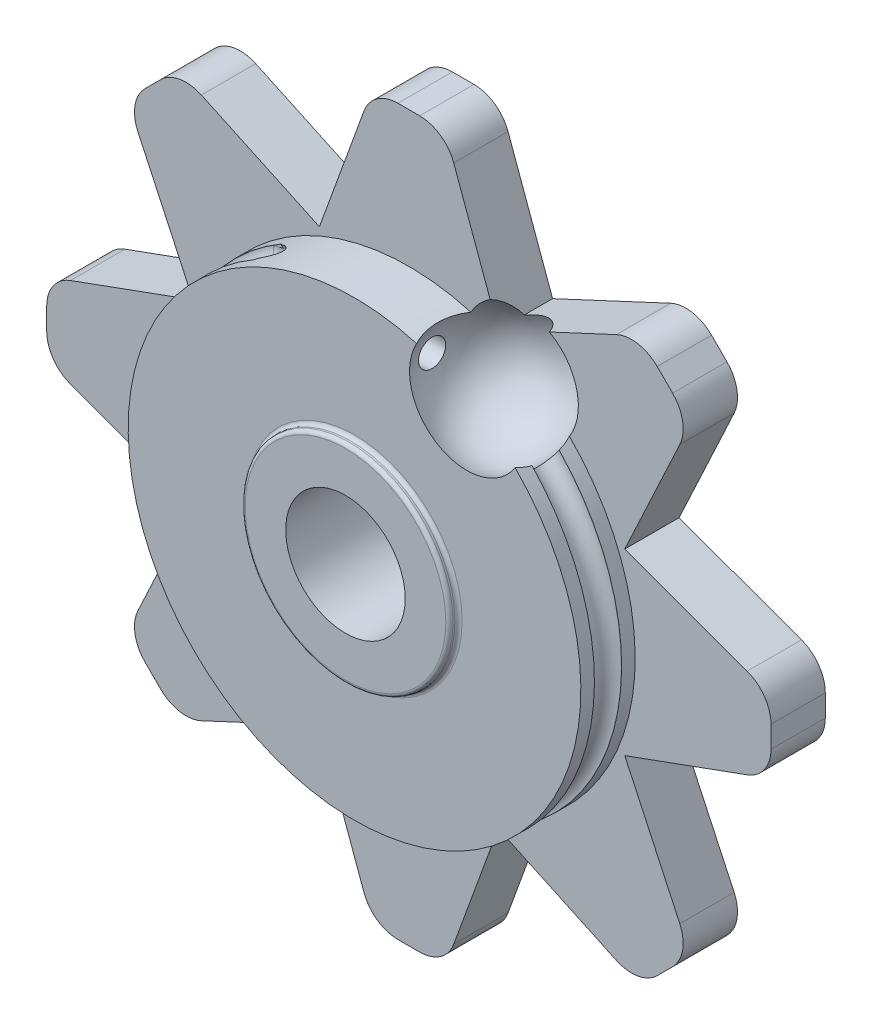
SolidWorks part; units mm, degrees
ref_plane "Front Plane" through (0, 0, 0) normal (0, 0, 1) x (1, 0, 0)
ref_plane "Top Plane" through (0, 0, 0) normal (0, 1, 0) x (1, 0, 0)
ref_plane "Right Plane" through (0, 0, 0) normal (1, 0, 0) x (0, 0, -1)
ref_axis "Axis1" through (-15.7375, 0, 0) along (1, 0, 0)
ref_axis "Axis2" through (0, 0, 2.1063) along (0, 0, -1)
ref_plane "Plane5" through (0, 0, 0) normal (0.866, 0.5, 0) x (0, 0, -1)
ref_plane "Plane6" through (3.1, 0, 0) normal (1, 0, 0) x (0, 0, -1)
sketch "Sketch1" plane through (0, 0, 0) normal (0, 0, 1) x (1, 0, 0)
  line L0 (-15.7375, 0) -> (15.7375, 0) construction
  circle A0 centre (0, 0) radius 6.25
  dimension "D1" = 12.5
extrude "body" add sketch "Sketch1" along normal blind 1.5 contours A0
sketch "Sketch2" plane through (0, 0, 0) normal (1, 0, 0) x (0, 0, -1)
  line L1 (0, 6.25) -> (-1.5, 6.25) construction
  line L2 (0, 5.25) -> (-1.5, 5.25) construction
  line L3 (-0.75, 5.25) -> (-0.75, -4.75) construction
  line L4 (0, -6.25) -> (0, 6.25) construction
  line L5 (0, -6.25) -> (0, 6.25) construction
  circle A0 centre (-0.75, 5.25) radius 0.375
  circle A1 centre (-0.75, -4.75) radius 0.375
  dimension "D1" = 0.75
  dimension "D3" = 0.75
  dimension "D4" = 1.5
  dimension "D2" = 1
extrude "Hole to trap cable knot" cut sketch "Sketch2" against normal through all and the other way blind 10 contours A0 | A1
ref_plane "Plane1" through (0, 0, 1.875) normal (0, 0, 1) x (1, 0, 0)
sketch "Sketch6" plane through (0, 0, 1.875) normal (0, 0, 1) x (1, 0, 0)
  line L0 (1.3991, -2.4232) -> (-1.3991, 2.4232) construction
  arc A0 (3.9111, 4.875) -> (2.7243, 5.625) centre (0, 0) ccw construction
  circle A2 centre (0, 0) radius 6.25 construction
  arc A3 (-3.125, 5.4127) -> (3.2608, 5.332) centre (0, 0) ccw
  arc A4 (3.9111, 4.875) -> (2.7243, 5.625) centre (0, 0) ccw construction
sketch "Sketch10" plane through (-5.4127, 9.375, 0) normal (-0.866, -0.5, 0) x (-0.5, 0.866, 0)
  line L0 (-4.5831, -1.125) -> (-3.8727, -1.125)
  line L1 (-3.8727, -1.125) -> (-3.8727, -0.3748)
  line L2 (-3.8727, -0.3748) -> (-4.5831, -0.3748)
  arc A0 (-4.5831, -0.3748) -> (-4.5831, -1.125) centre (-4.5831, -0.7499) ccw
  spline S0 degree 3 poles (-4.5903, -1.125) (-4.5759, -1.125) (-4.5739, -1.1025) (-4.5775, -1.0318) (-4.5799, -1.0018) (-4.5843, -0.9422) (-4.5859, -0.9199) (-4.589, -0.8665) (-4.5904, -0.8353) (-4.592, -0.7664) (-4.5919, -0.7281) (-4.5902, -0.6593) (-4.5887, -0.6289) (-4.5841, -0.5506) (-4.5809, -0.5129) (-4.5744, -0.422) (-4.574, -0.3902) (-4.5837, -0.3678) (-4.5938, -0.3778) (-4.6147, -0.4453) (-4.6227, -0.4771) (-4.6376, -0.5669) (-4.6447, -0.6281) (-4.6494, -0.7694) (-4.6461, -0.8461) (-4.6338, -0.9631) (-4.6257, -1.0065) (-4.603, -1.1026) (-4.5903, -1.125) (-4.5759, -1.125) (-4.5739, -1.1025) knots -0.125 -0.125 0 0 0.125 0.125 0.1875 0.1875 0.21875 0.21875 0.25 0.25 0.28125 0.28125 0.3125 0.3125 0.375 0.375 0.5 0.5 0.625 0.625 0.6875 0.6875 0.75 0.75 0.8125 0.8125 0.875 0.875 1 1 1.125 1.125 1.1875 only from (-4.5831, -1.125) to (-4.5831, -1.125) construction
  spline S1 degree 3 poles (-4.5903, -1.125) (-4.5759, -1.125) (-4.5739, -1.1025) (-4.5775, -1.0318) (-4.5799, -1.0018) (-4.5843, -0.9422) (-4.5859, -0.9199) (-4.589, -0.8665) (-4.5904, -0.8353) (-4.592, -0.7664) (-4.5919, -0.7281) (-4.5902, -0.6593) (-4.5887, -0.6289) (-4.5841, -0.5506) (-4.5809, -0.5129) (-4.5744, -0.422) (-4.574, -0.3902) (-4.5837, -0.3678) (-4.5938, -0.3778) (-4.6147, -0.4453) (-4.6227, -0.4771) (-4.6376, -0.5669) (-4.6447, -0.6281) (-4.6494, -0.7694) (-4.6461, -0.8461) (-4.6338, -0.9631) (-4.6257, -1.0065) (-4.603, -1.1026) (-4.5903, -1.125) (-4.5759, -1.125) (-4.5739, -1.1025) knots -0.125 -0.125 0 0 0.125 0.125 0.1875 0.1875 0.21875 0.21875 0.25 0.25 0.28125 0.28125 0.3125 0.3125 0.375 0.375 0.5 0.5 0.625 0.625 0.6875 0.6875 0.75 0.75 0.8125 0.8125 0.875 0.875 1 1 1.125 1.125 1.1875 only from (-4.5831, -1.125) to (-4.5831, -1.125) construction
  point P1 (-4.5831, -0.3748)
sweep "track for cable" cut profiles "Sketch10" path "Sketch6"
sketch "Sketch12" plane through (0, 0, 0) normal (0, 0, -1) x (-1, 0, 0)
  line L0 (0, 10) -> (0, -10) construction
  line L1 (-2.5653, 5.6993) -> (-1.2395, 9.342)
  line L2 (-0.2998, 10) -> (0.2998, 10)
  line L3 (1.2395, 9.342) -> (2.5653, 5.6993)
  line L6 (-3.2365, 3.8554) -> (3.2365, 3.8554) construction
  line L7 (-2.5653, 5.6993) -> (0, 0)
  line L8 (0, 0) -> (2.5653, 5.6993)
  arc A0 (-1.2395, 9.342) -> (-0.2998, 10) centre (-0.2998, 9) cw
  arc A1 (0.2998, 10) -> (1.2395, 9.342) centre (0.2998, 9) cw
  circle A4 centre (0, 0) radius 6.25 construction
  point P9 (-1, 10)
  point P12 (1, 10)
  dimension "D6" = 1
  dimension "D1" = 20
  dimension "D2" = 2
  dimension "D3" = 6.4729
  dimension "D4" = 110
  dimension "D5" = 110
sketch "Sketch14" plane through (0, 0, 0) normal (0, 0, -1) x (-1, 0, 0)
  line L0 (5.7294, 7.4823) -> (2.4696, 5.9622)
  line L1 (7.2831, 6.8591) -> (6.8591, 7.2831)
  line L2 (5.9622, 2.4696) -> (7.4823, 5.7294)
  line L3 (0, 0) -> (5.844, 2.216) construction
  line L4 (2.216, 5.844) -> (0, 0) construction
  line L5 (-1.2395, 9.342) -> (-2.5653, 5.6993)
  line L6 (0.2998, 10) -> (-0.2998, 10)
  line L7 (2.5653, 5.6993) -> (1.2395, 9.342)
  line L8 (0, 0) -> (2.5653, 5.6993)
  line L9 (0, 0) -> (2.5653, 5.6993) construction
  line L10 (-1.2395, 9.342) -> (-2.4696, 5.9622)
  line L11 (0.2998, 10) -> (-0.2998, 10)
  line L12 (2.4696, 5.9622) -> (1.2395, 9.342)
  line L13 (-2.5653, 5.6993) -> (0, 0)
  line L14 (-2.5653, 5.6993) -> (0, 0) construction
  line L15 (9.342, 1.2395) -> (5.9622, 2.4696)
  line L16 (10, -0.2998) -> (10, 0.2998)
  line L17 (5.9622, -2.4696) -> (9.342, -1.2395)
  line L18 (0, 0) -> (5.6993, -2.5653) construction
  line L19 (5.6993, 2.5653) -> (0, 0) construction
  line L20 (7.4823, -5.7294) -> (5.9622, -2.4696)
  line L21 (6.8591, -7.2831) -> (7.2831, -6.8591)
  line L22 (2.4696, -5.9622) -> (5.7294, -7.4823)
  line L23 (0, 0) -> (2.216, -5.844) construction
  line L24 (5.844, -2.216) -> (0, 0) construction
  line L25 (1.2395, -9.342) -> (2.4696, -5.9622)
  line L26 (-0.2998, -10) -> (0.2998, -10)
  line L27 (-2.4696, -5.9622) -> (-1.2395, -9.342)
  line L28 (0, 0) -> (-2.5653, -5.6993) construction
  line L29 (2.5653, -5.6993) -> (0, 0) construction
  line L30 (-5.7294, -7.4823) -> (-2.4696, -5.9622)
  line L31 (-7.2831, -6.8591) -> (-6.8591, -7.2831)
  line L32 (-5.9622, -2.4696) -> (-7.4823, -5.7294)
  line L33 (0, 0) -> (-5.844, -2.216) construction
  line L34 (-2.216, -5.844) -> (0, 0) construction
  line L35 (-9.342, -1.2395) -> (-5.9622, -2.4696)
  line L36 (-10, 0.2998) -> (-10, -0.2998)
  line L37 (-5.9622, 2.4696) -> (-9.342, 1.2395)
  line L38 (0, 0) -> (-5.6993, 2.5653) construction
  line L39 (-5.6993, -2.5653) -> (0, 0) construction
  line L40 (-7.4823, 5.7294) -> (-5.9622, 2.4696)
  line L41 (-6.8591, 7.2831) -> (-7.2831, 6.8591)
  line L42 (-2.4696, 5.9622) -> (-5.7294, 7.4823)
  line L43 (0, 0) -> (-2.216, 5.844) construction
  line L44 (-5.844, 2.216) -> (0, 0) construction
  arc A0 (6.8591, 7.2831) -> (5.7294, 7.4823) centre (6.152, 6.5759) ccw
  arc A1 (7.4823, 5.7294) -> (7.2831, 6.8591) centre (6.5759, 6.152) ccw
  arc A2 (-0.2998, 10) -> (-1.2395, 9.342) centre (-0.2998, 9) ccw
  arc A3 (1.2395, 9.342) -> (0.2998, 10) centre (0.2998, 9) ccw
  arc A4 (-0.2998, 10) -> (-1.2395, 9.342) centre (-0.2998, 9) ccw
  arc A5 (1.2395, 9.342) -> (0.2998, 10) centre (0.2998, 9) ccw
  arc A6 (10, 0.2998) -> (9.342, 1.2395) centre (9, 0.2998) ccw
  arc A7 (9.342, -1.2395) -> (10, -0.2998) centre (9, -0.2998) ccw
  arc A8 (7.2831, -6.8591) -> (7.4823, -5.7294) centre (6.5759, -6.152) ccw
  arc A9 (5.7294, -7.4823) -> (6.8591, -7.2831) centre (6.152, -6.5759) ccw
  arc A10 (0.2998, -10) -> (1.2395, -9.342) centre (0.2998, -9) ccw
  arc A11 (-1.2395, -9.342) -> (-0.2998, -10) centre (-0.2998, -9) ccw
  arc A12 (-6.8591, -7.2831) -> (-5.7294, -7.4823) centre (-6.152, -6.5759) ccw
  arc A13 (-7.4823, -5.7294) -> (-7.2831, -6.8591) centre (-6.5759, -6.152) ccw
  arc A14 (-10, -0.2998) -> (-9.342, -1.2395) centre (-9, -0.2998) ccw
  arc A15 (-9.342, 1.2395) -> (-10, 0.2998) centre (-9, 0.2998) ccw
  arc A16 (-7.2831, 6.8591) -> (-7.4823, 5.7294) centre (-6.5759, 6.152) ccw
  arc A17 (-5.7294, 7.4823) -> (-6.8591, 7.2831) centre (-6.152, 6.5759) ccw
  point P67 (0, 0)
  dimension "D1" = 0
  dimension "D2" = 8
extrude "thumb grip" add sketch "Sketch14" along normal blind 1.5
sketch "Sketch13" plane through (0, 0, 1.5) normal (0, 0, 1) x (1, 0, 0)
  circle A0 centre (0, 0) radius 1.65
  dimension "D1" = 3.3
extrude "hole for screw" cut sketch "Sketch13" against normal through all
sketch "Sketch20" plane through (3.1, 0, 0) normal (1, 0, 0) x (0, 0, -1)
  line L0 (-0.75, 7) -> (-0.75, 3.5)
  line L1 (-0.75, 7.7934) -> (-0.75, 1.6513) construction
  circle A0 centre (-0.75, 5.25) radius 1.75 construction
  arc A1 (-0.3841, 5.332) -> (-1.1159, 5.332) centre (-0.75, 5.25) ccw construction
  arc A2 (-0.3841, 5.332) -> (-1.1159, 5.332) centre (-0.75, 5.25) ccw construction
  arc A3 (-0.75, 7) -> (-0.75, 3.5) centre (-0.75, 5.25) cw
  dimension "D1" = 3.5
revolve "trap for ball" cut sketch "Sketch20" angle 360 about L1
sketch "Sketch21" plane through (0, 0, 1.5) normal (0, 0, 1) x (1, 0, 0)
  circle A0 centre (0, 0) radius 2.8716
  circle A3 centre (0, 0) radius 1.65 construction
  circle A4 centre (0, 0) radius 1.65
extrude "lip to contact handle" add sketch "Sketch21" along normal blind 0.25 and the other way blind 4.25
fillet "Fillet1" radius 0.1 4 edges at (2.8716, 0, 1.5) (2.8716, 0, 1.75) (-2.8716, 0, -1.5) (2.8716, 0, -2.75)
equation "\"Do\"=7.5mm"
equation "\"Lo\"=10"
equation "\"screw_diam\" = 3.5mm"
equation "\"wheel_Do\"=12.5mm"
equation "\"wheel_thickness\"=4mm"
equation "\"Collet_diameter\"=4.3"
equation "\"clearance\"= 0.5mm"
equation "\"D1@Sketch1\"=\"wheel_Do\""
equation "\"wheel_total_diam_ent\"=20"
equation "\"D1@Sketch12\"=\"wheel_total_diam_ent\""
equation "\"handle_body_width\" = 10mm"
equation "\"finger_diameter\"=35"
equation "\"collet_lid_diameter\"=10"
equation "\"screw_cap_diam\"=5.15"
equation "\"handle_thickness\"=12.5mm"
equation "\"post_hole_diam\"=2"
equation "\"roll_rod_diam\"= 6.5 "
equation "\"roll_rod_length\"=6.6"
equation "\"disc_diam\"=5"
equation "\"disc_width\"=1.5"
equation "\"arm_width\"=5"
equation "\"arm_thickness\"=4.5"
equation "\"wheel_total_diam\"=30"
equation "\"D1@thumb grip\"=\"wheel_thickness\"-2.5"
equation "\"D1@body\"=\"wheel_thickness\""
